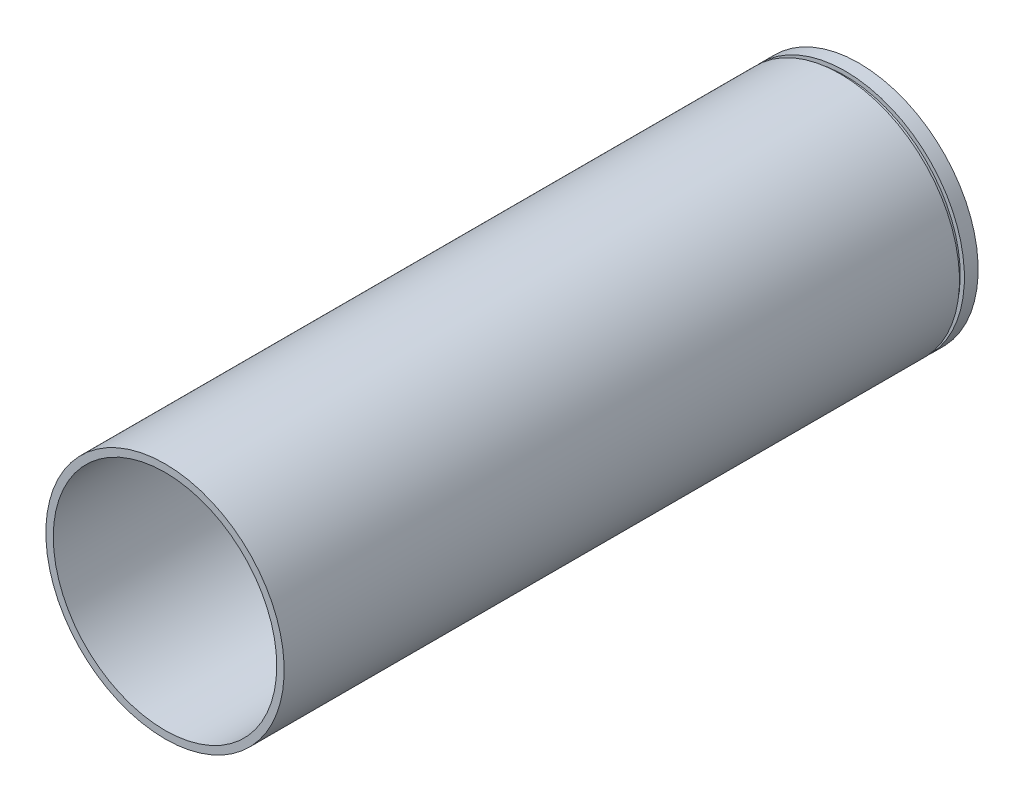
SolidWorks part; units mm, degrees
ref_plane "Front Plane" through (0, 0, 0) normal (0, 0, 1) x (1, 0, 0)
ref_plane "Top Plane" through (0, 0, 0) normal (0, 1, 0) x (1, 0, 0)
ref_plane "Right Plane" through (0, 0, 0) normal (1, 0, 0) x (0, 0, -1)
sketch "Sketch1" plane through (0, 0, 0) normal (1, 0, 0) x (0, 0, -1)
  line L0 (-63.9296, 0) -> (63.9296, 0) construction
  line L1 (283.3115, 101.3) -> (295, 101.3)
  line L2 (-295, 101.3) -> (279.1147, 101.3)
  line L3 (-295, 101.3) -> (-295, 95)
  line L4 (-295, 95) -> (295, 95)
  line L5 (295, 101.3) -> (295, 95)
  line L7 (279.1147, 101.3) -> (279.1147, 97.7791)
  line L8 (279.1147, 97.7791) -> (283.3115, 97.7791)
  line L9 (283.3115, 101.3) -> (283.3115, 97.7791)
  point P3 (0, 0)
  dimension "D1" = 95
  dimension "D2" = 6.3
  dimension "D3" = 590
revolve "Revolve2" add sketch "Sketch1" angle 360 about L0
